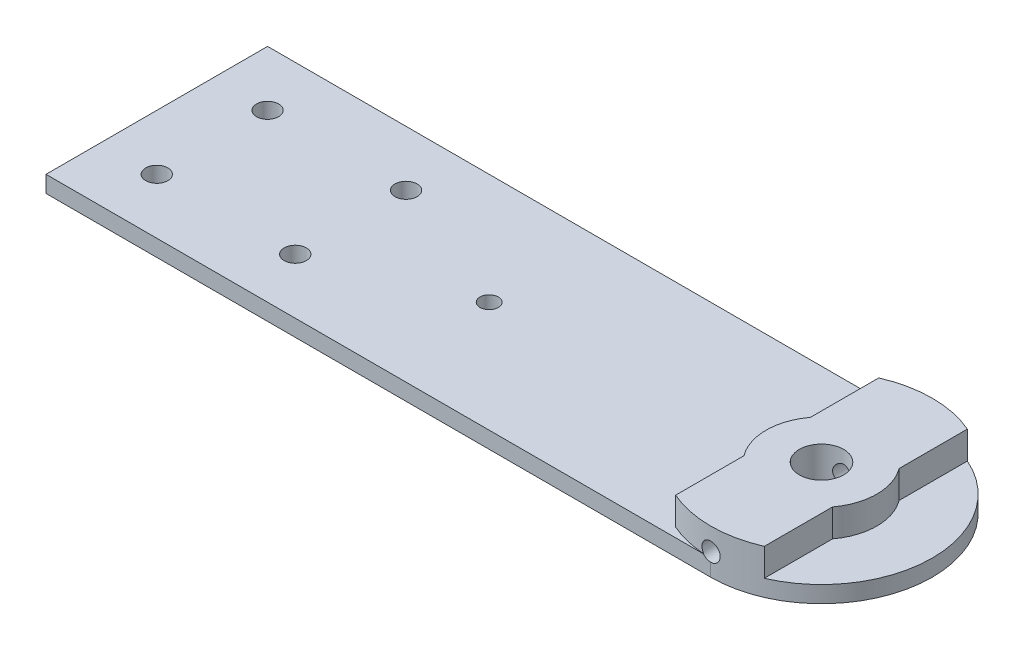
SolidWorks part; units mm, degrees
material "1060 Alloy"
ref_plane "Front Plane" through (0, 0, 0) normal (0, 0, 1) x (1, 0, 0)
ref_plane "Top Plane" through (0, 0, 0) normal (0, 1, 0) x (1, 0, 0)
ref_plane "Right Plane" through (0, 0, 0) normal (1, 0, 0) x (0, 0, -1)
sketch "Sketch1" plane through (0, 0, 0) normal (0, 1, 0) x (1, 0, 0)
  line L0 (-120, 20) -> (20, 20)
  line L1 (20, 20) -> (20, -5)
  line L2 (20, -5) -> (-120, -5) construction
  line L3 (-120, -5) -> (-120, 20)
  line L4 (20, -5) -> (20, -20)
  line L5 (20, -20) -> (-120, -20)
  line L6 (-120, -20) -> (-120, -5)
  line L7 (20, -10) -> (-110, -10) construction
  line L8 (-110, -10) -> (-110, -5) construction
  line L9 (-110, -5) -> (-110, 10) construction
  line L10 (-110, 10) -> (20, 10) construction
  circle A0 centre (0, 0) radius 4
  circle A1 centre (-110, 10) radius 2
  circle A2 centre (-85, 10) radius 2
  circle A3 centre (-85, -10) radius 2
  circle A4 centre (-110, -10) radius 2
  arc A5 (0, -20) -> (0, 20) centre (0, 0) ccw
  dimension "D1" = 8
  dimension "D7" = 4
  dimension "D2" = 20
  dimension "D3" = 25
  dimension "D4" = 20
  dimension "D5" = 15
  dimension "D6" = 140
  dimension "D9" = 25
  dimension "D8" = 10
extrude "Boss-Extrude1" add sketch "Sketch1" along normal blind 8 contours L5 A5 L0 L3 L6 A4 A3 A2 A1 A0 region at (-52.1353, 0, 0)
sketch "Sketch4" plane through (0, 8, 0) normal (0, 1, 0) x (1, 0, 0)
  line L0 (-8, 20) -> (-120, 20)
  line L1 (-120, 20) -> (-120, -20)
  line L2 (-120, -20) -> (-8, -20)
  line L3 (-120, 20) -> (0, 20) construction
  line L4 (0, -20) -> (-120, -20) construction
  line L5 (-8, 20) -> (-8, 6)
  line L6 (-8, -6) -> (-8, -20)
  line L7 (8, 18.3303) -> (8, 6)
  line L8 (8, -6) -> (8, -18.3303)
  arc A3 (8, -6) -> (8, 6) centre (0, 0) ccw
  arc A4 (0, -20) -> (0, 20) centre (0, 0) ccw construction
  arc A5 (-8, 6) -> (-8, -6) centre (0, 0) ccw
  circle M1 centre (-110, -10) radius 2
  circle M2 centre (-85, -10) radius 2
  circle M3 centre (-85, 10) radius 2
  circle M4 centre (-110, 10) radius 2
  line M6 (-120, -20) -> (0, -20)
  arc M7 (0, -20) -> (0, 20) centre (0, 0) ccw
  line M8 (0, 20) -> (-120, 20)
  line M9 (-120, 20) -> (-120, -20)
  dimension "D1" = 20
  dimension "D2" = 8
  dimension "D3" = 8
extrude "Cut-Extrude1" cut sketch "Sketch4" against normal offset from surface (5 mm away) 3 contours A5 L5 L6 M8 M9 M6 M2 M4 M3 M1 | A3 L8 L7 M7 region at (-63.8229, 8, 0) region at (13.175, 8, 0) up to face at (-110, 0, 12)
hole_wizard "M4 Tapped Hole1" positions "Sketch2" profile "Sketch3" tap size "M4" standard "ISO" end condition through all
sketch "Sketch2" plane through (0, 0, -20) normal (0, 0, -1) x (-1, 0, 0)
  line L0 (0, 4.4) -> (0, -4.4) construction
  line L1 (0, 8) -> (0, 0) construction
  point P0 (0, 4)
  point P11 (0, 4)
cosmetic thread "Hole Thread1" parameters "D2"=4
sketch "Sketch3" plane through (0, 4, -20) normal (1, 0, 0) x (0, 1, 0)
  line L0 (0, 0) -> (0, 40)
  line L1 (0, 40) -> (1.65, 40)
  line L2 (1.65, 40) -> (1.65, 0)
  line L5 (1.65, 0) -> (0, 0)
  line L11 (0, -6.35) -> (0, 107.95) construction
  dimension "Thru Tap Drill Dia." = 3.3
  dimension "Thru Tap Drill Depth" = 40
sketch "Sketch5" plane through (0, 3, 0) normal (0, 1, 0) x (1, 0, 0)
  circle A1 centre (-60, 0) radius 1.65
  dimension "D1" = 3.3
extrude "Cut-Extrude2" cut sketch "Sketch5" against normal through all
sketch "Sketch6" plane through (0, 8, 0) normal (0, 1, 0) x (1, 0, 0)
  line L6 (-120, -20) -> (0, -20)
  line L7 (-120, 20) -> (-120, -20)
  line L8 (0, 20) -> (-120, 20)
  line L9 (-120, -20) -> (0, -20)
  line L10 (-120, 20) -> (-120, -20)
  line L11 (0, 20) -> (-120, 20)
  arc A0 (0, 20) -> (0, -20) centre (0, 0) ccw
  arc A1 (0, -20) -> (0, 20) centre (0, 0) ccw construction
  arc A4 (0, -20) -> (0, 20) centre (0, 0) ccw
  dimension "D1" = 0
extrude "Cut-Extrude3" cut sketch "Sketch6" against normal up to surface (5 mm away) up to face at (-60, 3, 1.65)
